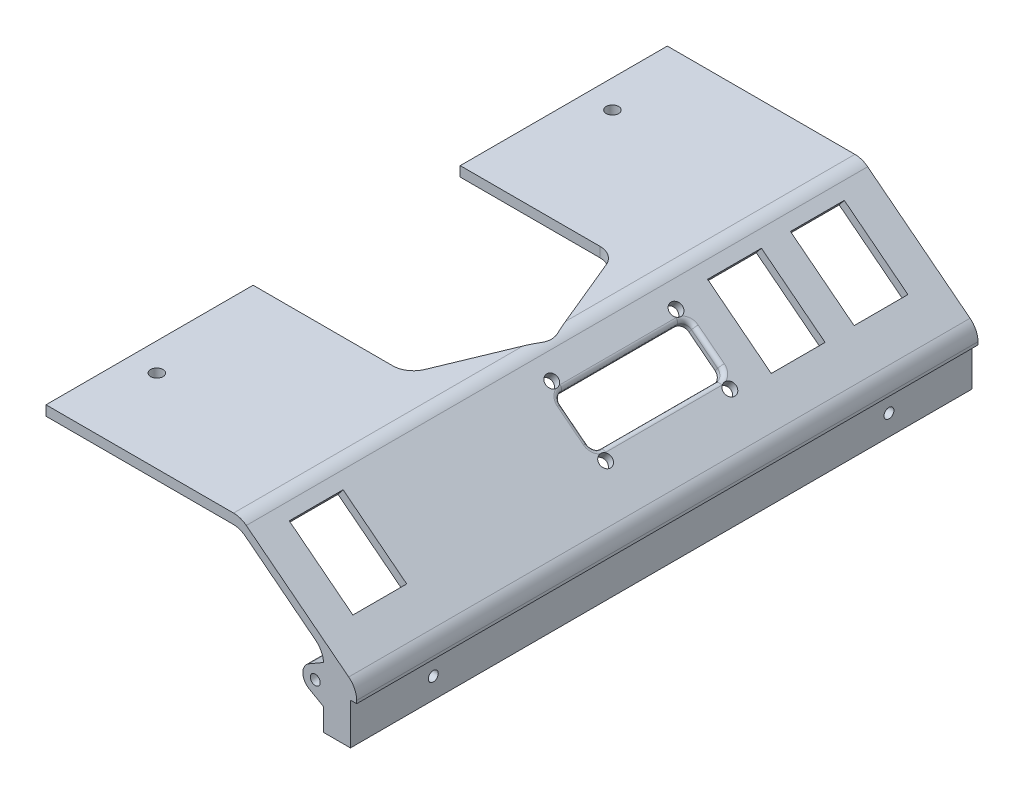
SolidWorks part; units mm, degrees
material "ABS"
ref_plane "Plan de face" through (0, 0, 0) normal (0, 0, 1) x (1, 0, 0)
ref_plane "Plan de dessus" through (0, 0, 0) normal (0, 1, 0) x (1, 0, 0)
ref_plane "Plan de droite" through (0, 0, 0) normal (1, 0, 0) x (0, 0, -1)
sketch "Esquisse1" plane through (0, 0, 0) normal (0, 0, 1) x (1, 0, 0)
  line L0 (0, 0) -> (47, 0)
  line L1 (47, 0) -> (75, -21.876)
  line L2 (75, -21.876) -> (75, -35)
  line L3 (75, -35) -> (67, -35)
  line L4 (67, -35) -> (67, -18.1637)
  line L5 (67, -18.1637) -> (46.8233, -2.4)
  line L6 (46.8233, -2.4) -> (0, -2.4)
  line L7 (0, -2.4) -> (0, 0)
  dimension "D1" = 75
  dimension "D2" = 28
  dimension "D3" = 38
  dimension "D4" = 35
  dimension "D5" = 2.4
  dimension "D6" = 8
  dimension "D7" = 2
extrude "Boss.-Extru.1" add sketch "Esquisse1" along normal mid plane 150
fillet "Congé1" radius 5 4 edges at (67, -18.1637, 0) (46.8233, -2.4, 0) (75, -21.876, 0) (47, 0, 0)
sketch "Esquisse2" plane through (0, 0, 75) normal (0, 0, 1) x (1, 0, 0)
  line L0 (45.2784, 0) -> (0, 0) construction
  line L1 (75, -35) -> (73.5, -35)
  line L2 (75, -35) -> (75, -25)
  line L3 (75, -25) -> (73.5, -25)
  line L4 (73.5, -35) -> (73.5, -25)
  dimension "D1" = 25
  dimension "D2" = 1.5
extrude "Enlèv. mat.-Extru.1" cut sketch "Esquisse2" against normal through all
sketch "Esquisse3" plane through (73.5, 0, 0) normal (1, 0, 0) x (0, 0, -1)
  line L0 (0, -35) -> (0, 0) construction
  line L1 (75, -35) -> (-75, -35) construction
  line L2 (75, -25) -> (-75, -25) construction
  circle A0 centre (-55, -30) radius 1.2
  circle A1 centre (55, -30) radius 1.2
  dimension "D1" = 110
  dimension "D2" = 5
  dimension "D3" = 2.4
extrude "Enlèv. mat.-Extru.2" cut sketch "Esquisse3" against normal through all
sketch "Esquisse4" plane through (67, 0, 0) normal (-1, 0, 0) x (0, 0, 1)
  line L0 (75, -35) -> (-75, -35) construction
  line L1 (57.75, -31.5877) -> (57.75, -28.4123)
  line L2 (57.75, -28.4123) -> (55, -26.8246)
  line L3 (55, -26.8246) -> (52.25, -28.4123)
  line L4 (52.25, -28.4123) -> (52.25, -31.5877)
  line L5 (52.25, -31.5877) -> (55, -33.1754)
  line L6 (55, -33.1754) -> (57.75, -31.5877)
  line L7 (-52.25, -31.5877) -> (-52.25, -28.4123)
  line L8 (-52.25, -28.4123) -> (-55, -26.8246)
  line L9 (-55, -26.8246) -> (-57.75, -28.4123)
  line L10 (-57.75, -28.4123) -> (-57.75, -31.5877)
  line L11 (-57.75, -31.5877) -> (-55, -33.1754)
  line L12 (-55, -33.1754) -> (-52.25, -31.5877)
  circle A0 centre (55, -30) radius 2.75 construction
  circle A1 centre (-55, -30) radius 2.75 construction
  circle A2 centre (55, -30) radius 5
  circle A3 centre (-55, -30) radius 5
  dimension "D1" = 5.5
extrude "Boss.-Extru.2" add sketch "Esquisse4" along normal blind 3
fillet "Congé2" radius 3 2 edges at (67, -30, 60) (67, -30, -50)
sketch "Esquisse5" plane through (0, 0, 75) normal (0, 0, 1) x (1, 0, 0)
  line L0 (75, -25) -> (75, -24.3147) construction
  line L1 (45.2784, 0) -> (0, 0) construction
  line L2 (73.0783, -20.3746) -> (48.3567, -1.0599) construction
  line L3 (67, -29.6188) -> (67, -20.3812)
  line L4 (67, -20.6024) -> (67, -35) construction
  line L5 (67, -20.3812) -> (63.5, -22.4019)
  line L6 (63.5, -27.5981) -> (67, -29.6188)
  circle A0 centre (65, -25) radius 1.2
  arc A1 (63.5, -22.4019) -> (63.5, -27.5981) centre (65, -25) ccw
  dimension "D1" = 10
  dimension "D2" = 25
  dimension "D3" = 8.6184
  dimension "D4" = 2.4
  dimension "D5" = 60
  dimension "D6" = 3
extrude "Boss.-Extru.3" add sketch "Esquisse5" against normal blind 10
mirror "Symétrie1" about plane through (0, 0, 0) normal (0, 0, 1) of "Boss.-Extru.3"
sketch "Esquisse6" plane through (0, 0, 0) normal (0, 1, 0) x (1, 0, 0)
  line L0 (0, -75) -> (0, 75) construction
  line L1 (0, 25) -> (33.7157, 25)
  line L2 (0, 25) -> (0, -25)
  line L3 (0, -25) -> (33.7157, -25)
  line L4 (42, 0) -> (0, 0) construction
  line L5 (38.3351, 21.9134) -> (46.6194, 1.9134)
  line L6 (46.6194, -1.9134) -> (38.3351, -21.9134)
  arc A0 (46.6194, 1.9134) -> (46.6194, -1.9134) centre (42, 0) cw
  arc A1 (33.7157, -25) -> (38.3351, -21.9134) centre (33.7157, -20) ccw
  arc A2 (33.7157, 25) -> (38.3351, 21.9134) centre (33.7157, 20) cw
  circle A3 centre (6.75, 55) radius 1.5
  circle A4 centre (6.75, -55) radius 1.5
  dimension "D1" = 50
  dimension "D2" = 5
  dimension "D4" = 5
  dimension "D5" = 42
  dimension "D6" = 3
  dimension "D7" = 6.75
  dimension "D8" = 110
  dimension "D3" = 135
extrude "Enlèv. mat.-Extru.4" cut sketch "Esquisse6" against normal through all
sketch "Esquisse7" plane through (17.8148, 22.8019, 0) normal (0.6157, 0.788, 0) x (0.788, -0.6157, 0)
  line L0 (51.7581, 26) -> (51.7581, 10) construction
  line L1 (45.7581, 26) -> (57.7581, 26)
  line L2 (45.7581, 26) -> (45.7581, -6)
  line L3 (45.7581, -6) -> (57.7581, -6)
  line L4 (57.7581, 26) -> (57.7581, -6)
  line L5 (51.7581, 10) -> (45.7581, 10) construction
  line L6 (38.7581, 75) -> (38.7581, -75) construction
  line L7 (70.1304, -75) -> (38.7581, -75) construction
  circle A0 centre (60.0081, 25) radius 1.5
  circle A1 centre (43.5081, 25) radius 1.5
  circle A2 centre (43.5081, -5) radius 1.5
  circle A3 centre (60.0081, -5) radius 1.5
  dimension "D1" = 13
  dimension "D2" = 16.5
  dimension "D3" = 30
  dimension "D7" = 3
  dimension "D4" = 32
  dimension "D5" = 12
  dimension "D6" = 85
extrude "Enlèv. mat.-Extru.5" cut sketch "Esquisse7" against normal blind 10
fillet "Congé3" radius 2 4 edges at (62.7132, -13.5455, 6) (53.2571, -6.1576, 6) (62.7132, -13.5455, -26) (53.2571, -6.1576, -26)
fillet "Congé4" radius 1 8 edges at (54.3344, -5.7302, -25.4142) (58.6008, -9.0635, -26) (62.8673, -12.3969, -25.4142) (63.3289, -12.7575, -10) (62.8673, -12.3969, 5.4142) (58.6008, -9.0635, 6) (54.3344, -5.7302, 5.4142) (53.8727, -5.3696, -10)
sketch "Esquisse8" plane through (17.8148, 22.8019, 0) normal (0.6157, 0.788, 0) x (0.788, -0.6157, 0)
  line L0 (38.7581, 75) -> (38.7581, -75) construction
  line L1 (41.7581, 47) -> (61.2581, 47)
  line L2 (41.7581, 47) -> (41.7581, 34)
  line L3 (41.7581, 34) -> (61.2581, 34)
  line L4 (61.2581, 47) -> (61.2581, 34)
  line L5 (41.7581, 67) -> (61.2581, 67)
  line L6 (41.7581, 67) -> (41.7581, 54)
  line L7 (41.7581, 54) -> (61.2581, 54)
  line L8 (61.2581, 67) -> (61.2581, 54)
  line L9 (41.7581, -54) -> (61.2581, -54)
  line L10 (41.7581, -54) -> (41.7581, -67)
  line L11 (41.7581, -67) -> (61.2581, -67)
  line L12 (61.2581, -54) -> (61.2581, -67)
  line L13 (70.1304, -75) -> (38.7581, -75) construction
  line L14 (70.1304, 75) -> (38.7581, 75) construction
  dimension "D1" = 13
  dimension "D2" = 19.5
  dimension "D3" = 3
  dimension "D4" = 8
  dimension "D6" = 8
  dimension "D7" = 7
extrude "Enlèv. mat.-Extru.6" cut sketch "Esquisse8" against normal blind 10
